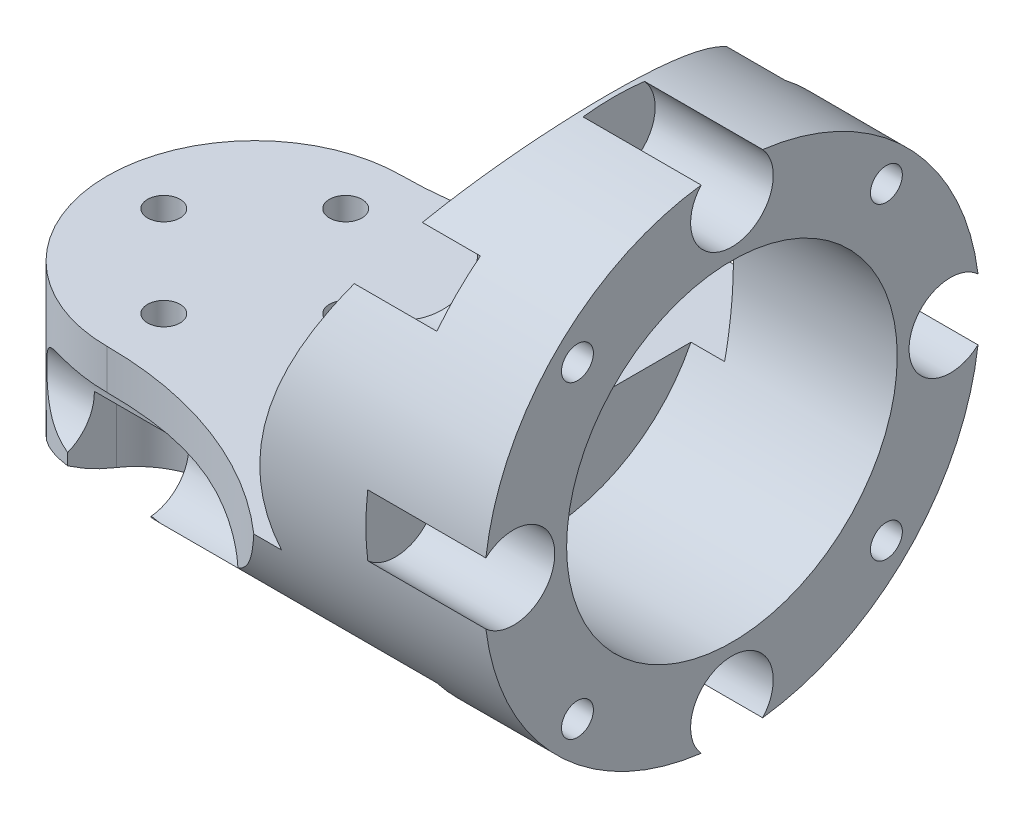
SolidWorks part; units mm, degrees
ref_plane "Front Plane" through (0, 0, 0) normal (0, 0, 1) x (1, 0, 0)
ref_plane "Top Plane" through (0, 0, 0) normal (0, 1, 0) x (1, 0, 0)
ref_plane "Right Plane" through (0, 0, 0) normal (1, 0, 0) x (0, 0, -1)
sketch "Sketch1" plane through (0, 0, 0) normal (0, 1, 0) x (1, 0, 0)
  line L0 (-7.7, 0) -> (0, 0) construction
  circle A0 centre (0, 0) radius 7.7 construction
  circle A1 centre (-7.7, 0) radius 1.375
  circle A3 centre (0, 7.7) radius 1.375
  circle A4 centre (7.7, 0) radius 1.375
  circle A5 centre (0, -7.7) radius 1.375
  circle A6 centre (0, 0) radius 12.5
  point P15 (0, 0)
  dimension "D1" = 15.4
  dimension "D2" = 2.75
  dimension "D4" = 25
  dimension "D3" = 4
extrude "Boss-Extrude1" add sketch "Sketch1" along normal blind 10
sketch "Sketch2" plane through (0, 10, 0) normal (0, 1, 0) x (1, 0, 0)
  line L0 (-34.4677, 0) -> (30.7737, 0) construction
  line L1 (23.1267, 23.2887) -> (40.4085, 23.2887)
  line L2 (0, 12.5) -> (0, 0) construction
  line L3 (23.1267, -23.2887) -> (40.4085, -23.2887)
  line L4 (40.4085, 23.2887) -> (40.4085, -23.2887)
  line L5 (40.4085, 20.9394) -> (40.4085, 1.5938) construction
  arc A0 (23.1267, 23.2887) -> (0, 12.5) centre (0, 42.6816) cw
  circle A1 centre (0, 0) radius 12.5 construction
  arc A2 (23.1267, -23.2887) -> (0, -12.5) centre (0, -42.6816) ccw
  arc A3 (0, 12.5) -> (0, -12.5) centre (0, 0) cw
extrude "Boss-Extrude2" add sketch "Sketch2" against normal blind 20
sketch "Sketch3" plane through (0, 0, 0) normal (0, -1, 0) x (1, 0, 0)
  line L0 (23.1267, -23.2887) -> (40.4085, -23.2887)
  line L1 (40.4085, -23.2887) -> (40.4085, 23.2887)
  line L2 (92.4683, 0) -> (42.5897, 0) construction
  line L3 (40.4085, 23.2887) -> (40.4085, -23.2887) construction
  line L4 (40.4085, 0) -> (30, 0) construction
  line L5 (23.1267, 23.2887) -> (40.4085, 23.2887)
  line L6 (40.4085, -23.2887) -> (23.1267, -23.2887) construction
  arc A0 (21.2136, 21.2128) -> (21.2136, -21.2128) centre (0, 0) cw
  arc A1 (-25.2519, -10.89) -> (-25.9472, 9.11) centre (0, 0) ccw construction
  arc A2 (23.1267, -23.2887) -> (0, -12.5) centre (0, -42.6816) ccw construction
  arc A4 (21.2136, -21.2128) -> (23.1267, -23.2887) centre (0, -42.6816) cw
  arc A5 (23.1267, -23.2887) -> (0, -12.5) centre (0, -42.6816) ccw construction
  arc A6 (21.2136, 21.2128) -> (23.1267, 23.2887) centre (0, 42.6816) ccw
  dimension "D1" = 30
extrude "Boss-Extrude3" add sketch "Sketch3" along normal blind 21 and the other way blind 45
sketch "Sketch12" plane through (0, 0, 0) normal (0, -1, 0) x (1, 0, 0)
  circle A0 centre (0, 7.7) radius 1.375 construction
  circle A1 centre (7.7, 0) radius 1.375 construction
  arc A2 (0, -12.5) -> (0, 12.5) centre (0, 0) ccw
  arc A3 (0, 12.5) -> (0, -12.5) centre (0, 0) ccw
  arc A4 (0, -12.5) -> (0, 12.5) centre (0, 0) ccw
  arc A5 (0, 12.5) -> (0, -12.5) centre (0, 0) ccw
  circle A6 centre (0, -7.7) radius 1.375 construction
  circle A7 centre (-7.7, 0) radius 1.375 construction
  circle A8 centre (0, 7.7) radius 1.375
  circle A9 centre (7.7, 0) radius 1.375
  circle A10 centre (0, -7.7) radius 1.375
  circle A11 centre (-7.7, 0) radius 1.375
  dimension "D1" = 0
extrude "Boss-Extrude4" add sketch "Sketch12" along normal up to surface (10 mm away) up to face at (16.3583, -10, 0)
sketch "Sketch4" plane through (40.4085, 0, 0) normal (1, 0, 0) x (0, 0, -1)
  circle A0 centre (0, 16.25) radius 21
  circle A1 centre (0, 16.25) radius 21 construction
  circle A2 centre (0, 16.25) radius 128.8341
  dimension "D1" = 42
extrude "Cut-Extrude1" cut sketch "Sketch4" against normal blind 61
sketch "Sketch5" plane through (40.4085, 0, 0) normal (1, 0, 0) x (0, 0, -1)
  line L0 (-31.0802, 16.25) -> (31.1368, 16.25) construction
  line L1 (0, 16.25) -> (13.0815, 29.3315) construction
  circle A0 centre (0, 16.25) radius 14
  circle A1 centre (0, 16.25) radius 21 construction
  circle A2 centre (13.0815, 29.3315) radius 1.35 construction
  circle A3 centre (18.5, 16.25) radius 3.5 construction
  circle A4 centre (0, 16.25) radius 18.5 construction
  point P12 (0, 0)
  point P16 (0, 0)
  point P17 (0, 0)
  point P18 (0, 0)
  dimension "D1" = 28
  dimension "D3" = 37
  dimension "D4" = 2.7
  dimension "D5" = 7
  dimension "D2" = 45
extrude "Cut-Extrude2" cut sketch "Sketch5" against normal blind 16
sketch "Sketch6" plane through (40.4085, 0, 0) normal (1, 0, 0) x (0, 0, -1)
  circle A0 centre (18.5, 16.25) radius 3.5 construction
  circle A1 centre (13.0815, 29.3315) radius 1.35 construction
  circle A2 centre (18.5, 16.25) radius 3.5 construction
  circle A3 centre (13.0815, 29.3315) radius 1.35
  circle A4 centre (13.0815, 3.1685) radius 1.35
  circle A5 centre (-13.0815, 3.1685) radius 1.35
  circle A6 centre (-13.0815, 29.3315) radius 1.35
  circle A7 centre (0, 16.25) radius 14 construction
  circle A8 centre (0, -2.25) radius 3.5 construction
  circle A9 centre (-18.5, 16.25) radius 3.5 construction
  circle A10 centre (0, 34.75) radius 3.5 construction
  point P6 (-8.8309, 39.8849)
  point P15 (0, 16.25)
  point P16 (0, 0)
  point P24 (0, 16.25)
  dimension "D1" = 4
  dimension "D2" = 4
extrude "Cut-Extrude3" cut sketch "Sketch6" against normal through all
sketch "Sketch8" plane through (40.4085, 0, 0) normal (1, 0, 0) x (0, 0, -1)
  circle A0 centre (18.5, 16.25) radius 3.5
  circle A1 centre (18.5, 16.25) radius 3.5 construction
extrude "Cut-Extrude4" cut sketch "Sketch8" against normal blind 10
ref_axis "Axis1" through (24.4085, 16.25, 0) along (1, 0, 0)
pattern_circular "CirPattern1" count 4 over 360 about axis through (24.4085, 16.25, 0) along (1, 0, 0) of "Cut-Extrude4"
ref_plane "Plane1" through (-15, 0, 0) normal (1, 0, 0) x (0, 0, -1)
sketch "Sketch9" plane through (-15, 0, 0) normal (1, 0, 0) x (0, 0, -1)
  circle A0 centre (13.0815, 29.3315) radius 1.35 construction
  circle A1 centre (-13.0815, 29.3315) radius 1.35 construction
  circle A2 centre (-13.0815, 3.1685) radius 1.35 construction
  circle A3 centre (13.0815, 3.1685) radius 1.35 construction
  circle A4 centre (13.0815, 29.3315) radius 1.35 construction
  circle A5 centre (-13.0815, 29.3315) radius 1.35 construction
  circle A6 centre (-13.0815, 3.1685) radius 1.35 construction
  circle A7 centre (13.0815, 3.1685) radius 1.35 construction
  circle A8 centre (13.0815, 29.3315) radius 3.5
  circle A9 centre (-13.0815, 3.1685) radius 3.5
  circle A10 centre (-13.0815, 29.3315) radius 3.5
  circle A11 centre (13.0815, 3.1685) radius 3.5
  point P19 (0, 0)
  point P20 (0, 0)
  point P21 (0, 0)
  dimension "D1" = 7
extrude "Cut-Extrude5" cut sketch "Sketch9" along normal blind 47
ref_plane "Plane2" through (0, -4.75, 0) normal (0, -1, 0) x (-1, 0, 0)
sketch "Sketch13" plane through (0, -4.75, 0) normal (0, -1, 0) x (-1, 0, 0)
  line L0 (-4, 7.7) -> (-4, 15.3399)
  line L1 (-4, 15.3399) -> (4, 15.3399)
  line L2 (4, 15.3399) -> (4, 7.7)
  circle A0 centre (0, 7.7) radius 1.375 construction
  arc A1 (4, 7.7) -> (-4, 7.7) centre (0, 7.7) ccw construction
  circle A4 centre (0, 7.7) radius 1.375 construction
  arc A8 (-4, 7.7) -> (4, 7.7) centre (0, 7.7) ccw
  dimension "D1" = 8
extrude "Cut-Extrude8" cut sketch "Sketch13" against normal blind 8
ref_axis "Axis2" through (0, -7.95, 0) along (0, 1, 0)
pattern_circular "CirPattern3" count 3 every 90 about axis through (0, -7.95, 0) along (0, 1, 0) of "Cut-Extrude8"
sketch "Sketch14" plane through (0, -4.75, 0) normal (0, -1, 0) x (-1, 0, 0)
  circle A0 centre (-7.7, 0) radius 1.375 construction
  circle A1 centre (-7.7, 0) radius 1.375 construction
  circle A2 centre (-7.7, 0) radius 4
  arc A3 (-4, 7.7) -> (4, 7.7) centre (0, 7.7) ccw construction
extrude "Cut-Extrude9" cut sketch "Sketch14" against normal blind 8
